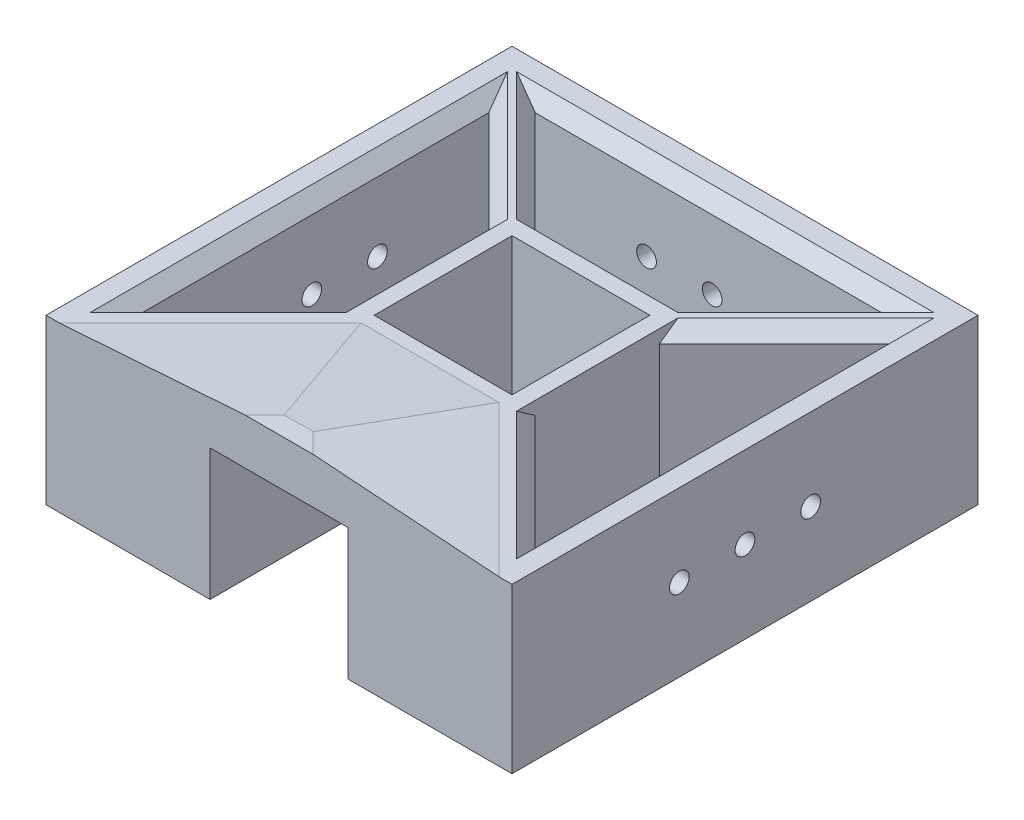
SolidWorks part; units mm, degrees
ref_plane "Front Plane" through (0, 0, 0) normal (0, 0, 1) x (1, 0, 0)
ref_plane "Top Plane" through (0, 0, 0) normal (0, 1, 0) x (1, 0, 0)
ref_plane "Right Plane" through (0, 0, 0) normal (1, 0, 0) x (0, 0, -1)
sketch "Sketch1" plane through (0, 0, 0) normal (0, 1, 0) x (1, 0, 0)
  line L0 (10.5, 35.5) -> (35.5, 35.5)
  line L1 (-10.5, -10.5) -> (10.5, -10.5)
  line L2 (-10.5, -10.5) -> (-10.5, 10.5)
  line L3 (-10.5, 10.5) -> (10.5, 10.5)
  line L4 (10.5, -10.5) -> (10.5, 10.5)
  line L5 (-10.5, -10.5) -> (10.5, 10.5) construction
  line L6 (-10.5, 10.5) -> (10.5, -10.5) construction
  line L7 (-13, -13) -> (13, -13)
  line L8 (-13, -13) -> (-13, 13)
  line L9 (-13, 13) -> (13, 13)
  line L10 (13, -13) -> (13, 13)
  line L11 (-13, -13) -> (13, 13) construction
  line L12 (-13, 13) -> (13, -13) construction
  line L13 (-10.5, 10.5) -> (-35.5, 10.5)
  line L14 (-10.5, 10.5) -> (-10.5, 35.5)
  line L15 (-10.5, 35.5) -> (-35.5, 35.5)
  line L16 (-35.5, 10.5) -> (-35.5, 35.5)
  line L17 (35.5, 10.5) -> (35.5, 35.5)
  line L18 (10.5, 10.5) -> (35.5, 10.5)
  line L19 (10.5, 10.5) -> (10.5, 35.5)
  line L20 (35.5, -10.5) -> (35.5, -35.5)
  line L21 (10.5, -35.5) -> (35.5, -35.5)
  line L22 (10.5, -10.5) -> (10.5, -35.5)
  line L23 (10.5, -10.5) -> (35.5, -10.5)
  line L24 (-10.5, -35.5) -> (-35.5, -35.5)
  line L25 (-35.5, -10.5) -> (-35.5, -35.5)
  line L26 (-10.5, -10.5) -> (-35.5, -10.5)
  line L27 (-10.5, -10.5) -> (-10.5, -35.5)
  line L28 (0, -1000) -> (0, 49000) construction
  line L29 (-35.5, 35.5) -> (35.5, 35.5)
  line L30 (-35.5, 35.5) -> (-35.5, 30.5)
  line L31 (-35.5, 30.5) -> (35.5, 30.5)
  line L32 (35.5, 35.5) -> (35.5, 30.5)
  line L33 (-35.5, 35.5) -> (-30.5, 35.5)
  line L34 (-35.5, 35.5) -> (-35.5, -35.5)
  line L35 (-35.5, -35.5) -> (-30.5, -35.5)
  line L36 (-30.5, 35.5) -> (-30.5, -35.5)
  line L37 (-1000, 0) -> (49000, 0) construction
  line L38 (-13, 9.4645) -> (-30.5, 26.9645)
  line L39 (-35.5, -35.5) -> (35.5, -35.5)
  line L40 (-35.5, -35.5) -> (-35.5, -30.5)
  line L41 (-35.5, -30.5) -> (35.5, -30.5)
  line L42 (35.5, -35.5) -> (35.5, -30.5)
  line L43 (35.5, -35.5) -> (30.5, -35.5)
  line L44 (35.5, -35.5) -> (35.5, 35.5)
  line L45 (35.5, 35.5) -> (30.5, 35.5)
  line L46 (30.5, -35.5) -> (30.5, 35.5)
  line L47 (-13, 9.4645) -> (-9.4645, 13)
  line L48 (-30.5, 26.9645) -> (-26.9645, 30.5)
  line L49 (-9.4645, 13) -> (-26.9645, 30.5)
  line L50 (13, 9.4645) -> (30.5, 26.9645)
  line L51 (9.4645, 13) -> (26.9645, 30.5)
  line L52 (26.9645, 30.5) -> (30.5, 26.9645)
  line L53 (9.4645, 13) -> (13, 9.4645)
  line L54 (9.4645, -13) -> (26.9645, -30.5)
  line L55 (13, -9.4645) -> (30.5, -26.9645)
  line L56 (30.5, -26.9645) -> (26.9645, -30.5)
  line L57 (13, -9.4645) -> (9.4645, -13)
  line L58 (-13, -9.4645) -> (-30.5, -26.9645)
  line L59 (-9.4645, -13) -> (-26.9645, -30.5)
  line L60 (-26.9645, -30.5) -> (-30.5, -26.9645)
  line L61 (-9.4645, -13) -> (-13, -9.4645)
  point P0 (0, 0)
  point P6 (0, 0)
  point P29 (0, 0)
  point P58 (0, 0)
  dimension "D1" = 21
  dimension "D2" = 26
  dimension "D3" = 25
  dimension "D5" = 5
  dimension "D6" = 5
  dimension "D7" = 5
  dimension "D8" = 5
  dimension "D9" = 5
  dimension "D4" = 4
  dimension "D10" = 4
extrude "Boss-Extrude1" add sketch "Sketch1" along normal blind 25 contours L1 L27 L7 L22 | L23 L22 L7 L10 | L4 L23 L10 L18 | L19 L18 L10 L9 | L3 L19 L9 L14 | L13 L14 L9 L8 | L26 L2 L13 L8 | L27 L26 L8 L7 | L41 L36 L24 L27 | L41 L34 L24 L36 | L25 L41 L36 L26 | L36 L13 L34 L26 | L36 L31 L16 L13 | L36 L29 L16 L31 | L15 L36 L31 L14 | L14 L31 L19 L29 | L31 L46 L0 L19 | L46 L31 L17 L29 | L46 L18 L17 L31 | L46 L23 L44 L18 | L46 L41 L20 L23 | L21 L46 L41 L22 | L46 L39 L20 L41 | L41 L27 L39 L22 | L14 L49 L48 L38 L13 L8 L9 | L36 L48 L31 | L8 L47 L13 | L38 L8 L13 | L47 L13 L14 | L14 L47 L9 | L9 L49 L14 | L9 L53 L19 | L53 L19 L18 | L31 L52 L46 | L57 L23 L22 | L7 L54 L22 | L22 L57 L7 | L10 L57 L23 | L55 L10 L23 | L56 L55 L23 L10 L7 L22 L54 | L46 L56 L41 | L60 L59 L27 L7 L8 L26 L58 | L8 L58 L26 | L26 L61 L8 | L61 L27 L26 | L7 L61 L27 | L59 L7 L27 | L41 L60 L36 | L54 L22 L41 | L7 L59 L27 L41 L22 L54 | L27 L59 L41 | L51 L52 L50 L53 region at (20.5, 0, -33) region at (0, 0, -33) region at (33, 0, -33) region at (-20.5, 0, -33) region at (29.3215, 0, -29.3215) region at (33, 0, -20.5) region at (-33, 0, -33) region at (10.1548, 0, -12.6548) region at (11.9078, 0, -11.9078) region at (0, 0, -11.7311) region at (-10.1548, 0, -13.3452) region at (-20.4962, 0, -20.4962) region at (-29.3215, 0, -29.3215) region at (-33, 0, -20.5) region at (33, 0, 0) region at (10.9882, 0, -10.9882) region at (-10.1548, 0, -12.6548) region at (-11.9078, 0, -11.9078) region at (33, 0, 20.5) region at (11.7311, 0, 0) region at (-10.9882, 0, -10.9882) region at (-33, 0, 0) region at (-13.3452, 0, -10.1548) region at (33, 0, 33) region at (20.4962, 0, 20.4962) region at (13.3452, 0, 10.1548) region at (29.3215, 0, 29.3215) region at (12.6548, 0, 10.1548) region at (-11.7311, 0, 0) region at (0, 0, 11.7311) region at (10.9882, 0, 10.9882) region at (-12.6548, 0, -10.1548) region at (-33, 0, 20.5) region at (20.5, 0, 33) region at (11.9078, 0, 11.9078) region at (15.9882, 0, 25.0118) region at (-10.9882, 0, 10.9882) region at (10.1548, 0, 12.6548) region at (-13.3452, 0, 10.1548) region at (-20.4962, 0, 20.4962) region at (-29.3215, 0, 29.3215) region at (-12.6548, 0, 10.1548) region at (-33, 0, 33) region at (0, 0, 21.7746) region at (0, 0, 33) region at (10.1548, 0, 13.3452) region at (-11.9078, 0, 11.9078) region at (-10.1548, 0, 12.6548) region at (-20.5, 0, 33) region at (-15.9882, 0, 25.0118) region at (-10.1548, 0, 13.3452)
sketch "Sketch2" plane through (0, 25, 0) normal (0, 1, 0) x (1, 0, 0)
  line L0 (10.5, -10.5) -> (10.5, 10.5) construction
  line L1 (-10.5, -35.5) -> (10.5, -35.5)
  line L2 (-10.5, -35.5) -> (-10.5, -12.5)
  line L3 (-10.5, -12.5) -> (10.5, -12.5)
  line L4 (10.5, -35.5) -> (10.5, -12.5)
  line L5 (-10.5, -10.5) -> (-10.5, 10.5) construction
  line L7 (-35.5, -35.5) -> (35.5, -35.5) construction
  line L8 (-10.5, -10.5) -> (10.5, -10.5) construction
  line L9 (10.5, -12.5) -> (33.5, -35.5)
  line L10 (13, -9.4645) -> (30.5, -26.9645) construction
  line L11 (-10.5, -12.5) -> (-33.5, -35.5)
  line L12 (-13, -9.4645) -> (-30.5, -26.9645) construction
  line M18 (-35.5, -35.5) -> (35.5, -35.5)
  dimension "D1" = 2
extrude "Boss-Extrude2" add sketch "Sketch2" along normal blind 2 contours L2 L11 M18 | L4 L3 L2 M18 | L9 L4 M18 region at (0, 25, 24) region at (-18.1667, 25, 27.8333) region at (18.1667, 25, 27.8333)
chamfer "Chamfer1" distance 20 distance2 2 3 edges at (22, 27, 24) (0, 27, 12.5) (-22, 27, 24) first distance on face at (0, 27, 24)
sketch "Sketch3" plane through (-35.5, 0, 0) normal (-1, 0, 0) x (0, 0, 1)
  line L0 (0, 0) -> (0, 25) construction
  line L4 (-35.5, 0) -> (35.5, 0)
  line L5 (35.5, 0) -> (35.5, 25)
  line L6 (35.5, 25) -> (-35.5, 25)
  line L7 (-35.5, 25) -> (-35.5, 0)
  line L8 (-35.5, 0) -> (35.5, 0)
  line L9 (35.5, 0) -> (35.5, 25)
  line L10 (35.5, 25) -> (-35.5, 25)
  line L11 (-35.5, 25) -> (-35.5, 0)
  circle A0 centre (0, 12.5) radius 1.5
  circle A1 centre (-10, 12.5) radius 1.5
  circle A2 centre (10, 12.5) radius 1.5
  point P9 (-8.9819, 10)
  dimension "D2" = 3
  dimension "D4" = 10
  dimension "D1" = 0
  dimension "D3" = 2
extrude "Cut-Extrude1" cut sketch "Sketch3" against normal blind 5 and the other way through all contours A1 | L0 A0 | A2 | A0 L0 region at (-35.5, 12.5, -0.6366) region at (-35.5, 12.5, 0.6366) region at (-35.5, 12.5, -10) region at (-35.5, 12.5, 10)
sketch "Sketch4" plane through (0, 0, -35.5) normal (0, 0, -1) x (-1, 0, 0)
  line L0 (0, 25) -> (0, 0) construction
  line L1 (-35.5, 12.5) -> (35.5, 12.5) construction
  line L4 (-35.5, 0) -> (35.5, 0)
  line L5 (35.5, 0) -> (35.5, 25)
  line L6 (35.5, 25) -> (-35.5, 25)
  line L7 (-35.5, 25) -> (-35.5, 0)
  line L8 (-35.5, 0) -> (35.5, 0)
  line L9 (35.5, 0) -> (35.5, 25)
  line L10 (35.5, 25) -> (-35.5, 25)
  line L11 (-35.5, 25) -> (-35.5, 0)
  circle A0 centre (0, 12.5) radius 1.5
  circle A1 centre (10, 12.5) radius 1.5
  circle A2 centre (-10, 12.5) radius 1.5
  dimension "D2" = 3
  dimension "D4" = 10
  dimension "D5" = 3
  dimension "D6" = 10
  dimension "D1" = 0
  dimension "D3" = 2
extrude "Cut-Extrude2" cut sketch "Sketch4" against normal blind 5 contours A2 | A0 | A1 region at (0, 12.5, -35.5) region at (-10, 12.5, -35.5) region at (10, 12.5, -35.5)
sketch "Sketch5" plane through (35.5, 0, 0) normal (1, 0, 0) x (0, 0, -1)
  line L0 (0, 25) -> (0, 0) construction
  line L4 (-35.5, 0) -> (35.5, 0)
  line L5 (35.5, 0) -> (35.5, 25)
  line L6 (35.5, 25) -> (-35.5, 25)
  line L7 (-35.5, 25) -> (-35.5, 0)
  line L8 (-35.5, 0) -> (35.5, 0)
  line L9 (35.5, 0) -> (35.5, 25)
  line L10 (35.5, 25) -> (-35.5, 25)
  line L11 (-35.5, 25) -> (-35.5, 0)
  circle A0 centre (0, 12.5) radius 1.5
  circle A1 centre (10, 12.5) radius 1.5
  circle A2 centre (-10, 12.5) radius 1.5
  dimension "D2" = 3
  dimension "D6" = 10
  dimension "D4" = 10
  dimension "D1" = 0
  dimension "D3" = 2
  dimension "D5" = 2
extrude "Cut-Extrude3" cut sketch "Sketch5" against normal blind 5 contours A2 | A0 L0 | L0 A0 | A1 region at (35.5, 12.5, -0.6366) region at (35.5, 12.5, 0.6366) region at (35.5, 12.5, -10) region at (35.5, 12.5, 10)
sketch "Sketch6" plane through (0, 0, 35.5) normal (0, 0, 1) x (1, 0, 0)
  line L0 (-35.5, 0) -> (35.5, 0) construction
  line L1 (-10.5, 0) -> (10.5, 0)
  line L2 (-10.5, 0) -> (-10.5, 20)
  line L3 (-10.5, 20) -> (10.5, 20)
  line L4 (10.5, 0) -> (10.5, 20)
  line L5 (0, 0) -> (0, 27) construction
  line L6 (-5.2157, 27) -> (5.2157, 27) construction
  circle A0 centre (0, 10) radius 2.5
  dimension "D4" = 5
  dimension "D1" = 10.5
  dimension "D2" = 10.5
  dimension "D3" = 20
extrude "Cut-Extrude4" cut sketch "Sketch6" against normal blind 21
extrude "Cut-Extrude5" cut sketch "Sketch6<2>" against normal blind 30 contours L5 A0 | A0 L5 region at (-1.061, 10, 35.5) region at (1.061, 10, 35.5)
sketch "Sketch6<2>" plane through (0, 0, 35.5) normal (0, 0, 1) x (1, 0, 0) same geometry as "Sketch6"
chamfer "Chamfer2" distance 2 angle 45 9 edges at (21.75, 25, -18.2145) (30.5, 25, 0) (21.75, 25, 18.2145) (-21.75, 25, 18.2145) (-30.5, 25, 0) (-21.75, 25, -18.2145) (-18.2145, 25, -21.75) (0, 25, -30.5) (18.2145, 25, -21.75)
